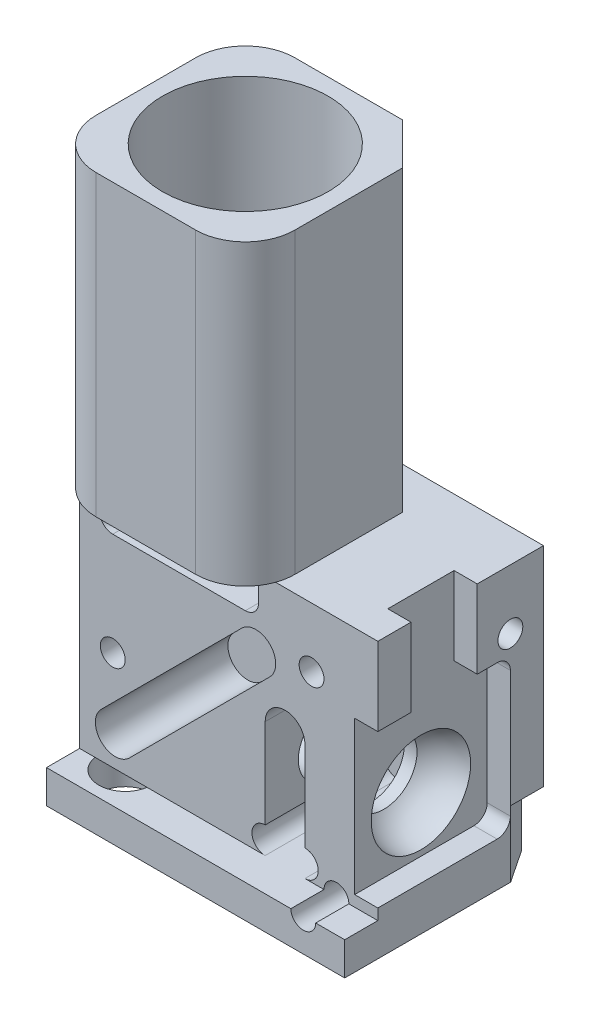
SolidWorks part; units mm, degrees
ref_plane "Front Plane" through (0, 0, 0) normal (0, 0, 1) x (1, 0, 0)
ref_plane "Top Plane" through (0, 0, 0) normal (0, 1, 0) x (1, 0, 0)
ref_plane "Right Plane" through (0, 0, 0) normal (1, 0, 0) x (0, 0, -1)
sketch "Sketch1" plane through (0, 0, 0) normal (0, 1, 0) x (1, 0, 0)
  line L1 (4.5, 3) -> (-4.5, 3)
  line L2 (4.5, 3) -> (4.5, -3)
  line L3 (4.5, -3) -> (-4.5, -3)
  line L4 (-4.5, 3) -> (-4.5, -3)
  line L5 (4.5, 3) -> (-4.5, -3) construction
  line L6 (4.5, -3) -> (-4.5, 3) construction
  point P0 (0, 0)
  dimension "D1" = 6
  dimension "D2" = 9
extrude "Main Body Ext" add sketch "Sketch1" along normal blind 8.3
sketch "Sketch8" plane through (0, 8.3, 0) normal (0, 1, 0) x (1, 0, 0)
  line L0 (0.25, 3) -> (1.5, 1.75)
  line L1 (0.25, 3) -> (-4.5, 3)
  line L2 (1.5, 1.75) -> (1.5, -3)
  line L3 (1.5, -3) -> (-4.5, -3)
  line L4 (-4.5, 3) -> (-4.5, -3)
  line L5 (0.875, 2.375) -> (-4.5, -3) construction
  line L6 (1.5, -3) -> (-4.5, 3) construction
  line L7 (-4.5, 3) -> (-4.5, -3) construction
  line L8 (0, 0) -> (-1.5, 0) construction
  point P0 (-1.5, 0)
  dimension "D1" = 6
  dimension "D2" = 6
  dimension "D3" = 1.25
  dimension "D4" = 3
extrude "Emission Path Ext" add sketch "Sketch8" along normal blind 9
sketch "Sketch3" plane through (0, 0, 0) normal (0, -1, 0) x (1, 0, 0)
  line L0 (-4.5, -3) -> (-4.5, 3) construction
  line L1 (0, 0) -> (-1.5, 0) construction
  circle A0 centre (-1.5, 0) radius 1.25
  dimension "D1" = 3
  dimension "D2" = 2.5
extrude "Emission and Grin Cut" cut sketch "Sketch3" against normal through all
sketch "Sketch4" plane through (4.5, 0, 0) normal (1, 0, 0) x (0, 0, -1)
  line L1 (-3, 0) -> (3, 0) construction
  circle A0 centre (0, 3) radius 1
  dimension "D1" = 2
  dimension "D2" = 3
extrude "Drum Lens Cut" cut sketch "Sketch4" against normal offset from surface (7 mm away) 2 up to face at (-4.5, 8.65, 0)
sketch "Sketch5" plane through (0, 0, 3) normal (0, 0, 1) x (1, 0, 0)
  line L0 (-4.5, 0) -> (4.5, 0) construction
  line L1 (4.5, 8.3) -> (-4.5, 8.3)
  line L2 (4.5, 8.3) -> (4.5, 1)
  line L3 (4.5, 1) -> (-4.5, 1)
  line L4 (-4.5, 8.3) -> (-4.5, 1)
  line L5 (4.5, 8.3) -> (-4.5, 1) construction
  line L6 (4.5, 1) -> (-4.5, 8.3) construction
  line L7 (1.5, 8.3) -> (4.5, 8.3) construction
  line L9 (4.5, 8.3) -> (4.5, 0) construction
  line L10 (-4.5, 17.3) -> (-4.5, 0) construction
  point P0 (0, 4.65)
  dimension "D1" = 1
extrude "FilterSet Cut1" cut sketch "Sketch5" against normal blind 1
sketch "Sketch6" plane through (0, 0, 2) normal (0, 0, 1) x (1, 0, 0)
  line L0 (2.3, 4.5) -> (2.3, 1.8)
  line L1 (1.1, 4.5) -> (2.3, 4.5) construction
  line L2 (2.3, 1) -> (1.1, 1)
  line L3 (-4.5, 1) -> (4.5, 1) construction
  line L4 (-4.5, 8.3) -> (-4.5, 1) construction
  line L5 (-3.9, 7.9) -> (-3.9, 7.5)
  line L6 (1.1, 4.5) -> (1.1, 1.8)
  line L7 (1.5, 8.3) -> (-4.5, 8.3) construction
  line L8 (0.9, 7.9) -> (0.9, 7.5)
  line L9 (-3, 1.5) -> (-3, 1) construction
  line L10 (0.5, 8.3) -> (-3.5, 8.3)
  line L11 (-1.5, 3) -> (-1.5, 1) construction
  line L12 (-1.5, 3) -> (0.4851, 3) construction
  line L13 (0.5, 7.1) -> (-3.5, 7.1)
  line L15 (0.5, 8.3) -> (-3.5, 7.1) construction
  line L16 (0.5, 7.1) -> (-3.5, 8.3) construction
  line L17 (1.1, 1.8) -> (2.3, 1.8) construction
  line L18 (0.3941, 6.5912) -> (-3.8485, 2.3485)
  line L19 (4.5, 1) -> (4.5, 8.3) construction
  line L20 (1.2426, 5.7426) -> (-3, 1.5)
  line L21 (0.3941, 6.5912) -> (-3, 1.5) construction
  line L22 (-3.8485, 2.3485) -> (1.2426, 5.7426) construction
  line L33 (0.5, 8.3) -> (1.102, 8.3) construction
  line L34 (1.102, 8.3) -> (1.102, 7.1) construction
  line L35 (1.102, 7.1) -> (0.5, 7.1) construction
  line L36 (-3.5, 7.1) -> (-4.098, 7.1) construction
  line L37 (-4.098, 7.1) -> (-4.098, 8.3) construction
  line L38 (-4.098, 8.3) -> (-3.5, 8.3) construction
  line L39 (-3.5, 8.3) -> (-2.7284, 6.992) construction
  arc A0 (0.5, 8.3) -> (0.9, 7.9) centre (0.5, 7.9) cw
  arc A1 (1.1, 4.5) -> (2.3, 4.5) centre (1.7, 4.5) cw
  arc A2 (-3.5, 8.3) -> (-3.9, 7.9) centre (-3.5, 7.9) ccw
  arc A3 (0.3941, 6.5912) -> (1.2426, 5.7426) centre (0.8184, 6.1669) cw
  arc A4 (1.1, 1) -> (1.1, 1.8) centre (1.1, 1.4) cw
  arc A5 (-3.8485, 2.3485) -> (-3, 1.5) centre (-3.4243, 1.9243) ccw
  arc A6 (2.3, 1) -> (2.3, 1.8) centre (2.3, 1.4) ccw
  arc A7 (-3.5, 7.1) -> (-3.9, 7.5) centre (-3.5, 7.5) cw
  arc A8 (0.5, 7.1) -> (0.9, 7.5) centre (0.5, 7.5) ccw
  point P5 (-1.5, 7.7)
  point P10 (-1.3029, 4.0456)
  dimension "D10" = 0.5
  dimension "D5" = 2.2
  dimension "D8" = 0.4
  dimension "D11" = 0.4
  dimension "D12" = 0.4
  dimension "D1" = 1.2
  dimension "D2" = 45
  dimension "D3" = 3.5
  dimension "D4" = 1.2
  dimension "D6" = 2
  dimension "D7" = 4
  dimension "D9" = 3
  dimension "D13" = 1.2
  dimension "D14" = 3
  dimension "D15" = 6
extrude "FilterSet Cut2" cut sketch "Sketch6" against normal offset from surface (4 mm away) 1 up to face at (0.4375, 9.2833, -3)
sketch "Sketch10" plane through (0, 17.3, 0) normal (0, 1, 0) x (1, 0, 0)
  line L0 (-1.5, 0) -> (-1.5, -3) construction
  line L1 (-4.5, -3) -> (1.5, -3) construction
  line L3 (-1.5, 0) -> (-4.5, 0) construction
  line L4 (-4.5, 3) -> (-4.5, -3) construction
  circle A0 centre (-1.5, 0) radius 2.5
  dimension "D1" = 5
extrude "Emission Lens Cut" cut sketch "Sketch10" against normal offset from surface (8.5 mm away) 0.5 up to face at (-1.125, 8.3, 1.3125)
sketch "Sketch12" plane through (4.5, 0, 0) normal (1, 0, 0) x (0, 0, -1)
  line L0 (0, 3.635) -> (0, 0) construction
  line L1 (1.6, 5.94) -> (-1.6, 5.94)
  line L2 (1.6, 5.94) -> (1.6, 1.33) construction
  line L3 (-2, 1.33) -> (1.6, 1.33)
  line L4 (-1.6, 5.94) -> (-1.6, 1.33) construction
  line L5 (1.6, 5.94) -> (-1.6, 1.33) construction
  line L6 (1.6, 1.33) -> (-1.6, 5.94) construction
  line L7 (-3, 0) -> (3, 0) construction
  line L9 (-1.6, 5.94) -> (-2, 5.94)
  line L10 (-2, 1) -> (-2, 8.3) construction
  line L11 (-2, 5.94) -> (-2, 1.33)
  line L12 (2, 5.54) -> (2, 1.73)
  arc A1 (1.6, 5.94) -> (2, 5.54) centre (1.6, 5.54) cw
  arc A2 (1.6, 1.33) -> (2, 1.73) centre (1.6, 1.73) ccw
  circle A3 centre (0, 3) radius 1 construction
  point P0 (0, 3.635)
  dimension "D2" = 4.61
  dimension "D3" = 1.67
  dimension "D1" = 3.2
  dimension "D4" = 0.4
sketch "Sketch15" plane through (0, 0, 0) normal (0, -1, 0) x (1, 0, 0)
  line L0 (-3.25, 1.875) -> (-3.25, -1.875) construction
  line L2 (1.5, 0) -> (-1.5, 0) construction
  line L3 (-1.5, 0) -> (-3.25, 0) construction
  circle A0 centre (-3.25, -1.875) radius 0.795
  circle A1 centre (-3.25, 1.875) radius 0.795
  circle A2 centre (1.5, 0) radius 0.795
  dimension "D4" = 1.59
  dimension "D1" = 3.75
  dimension "D2" = 3
  dimension "D3" = 1.75
extrude "Magnets Cut" cut sketch "Sketch15" against normal blind 1
sketch "Sketch18" plane through (0, 0, 2) normal (0, 0, 1) x (1, 0, 0)
  line L0 (-4.5, 8.3) -> (-4.5, 1) construction
  line L1 (4.5, 1) -> (4.5, 8.3) construction
  line L2 (4.5, 8.3) -> (1.5, 8.3) construction
  line L3 (-4.5, 0) -> (4.5, 0) construction
  line L7 (-4.5, 1) -> (-4.0351, 1) construction
  line L9 (-4.5, 1) -> (-4.5, 0) construction
  circle A0 centre (-3.5, 4) radius 0.375
  circle A1 centre (2.5, 6.5) radius 0.375
  circle A2 centre (3.25, 1) radius 0.375
  dimension "D1" = 0.75
  dimension "D2" = 1
  dimension "D3" = 1.8
  dimension "D4" = 2
  dimension "D5" = 3
  dimension "D6" = 1
  dimension "D7" = 7.75
extrude "Screw Holes Cut" cut sketch "Sketch18" against normal blind 3 and the other way through all
fillet "External Fillet 1" radius 1.5 2 edges at (-4.5, 8.65, -3)
sketch "Sketch14" plane through (0, 0, 0) normal (0, -1, 0) x (1, 0, 0)
  line L0 (4.5, -3) -> (4.5, -2.0067)
  line L1 (4.5, 3) -> (4.5, -3) construction
  line L2 (4.5, -2.0067) -> (3.8378, -3)
  line L3 (4.5, -3) -> (-3, -3) construction
  line L4 (3.8378, -3) -> (4.5, -3)
  line L5 (4.5, -3) -> (-4.5, 3) construction
  line L6 (-4.5, -1.5) -> (-4.5, 3) construction
  line L7 (-4.5, 3) -> (4.5, 3) construction
  dimension "D1" = 1.1938
sketch "Sketch28" plane through (0, 7.1, 0) normal (0, 1, 0) x (1, 0, 0)
  circle A0 centre (-1.5, 0) radius 1.5
  dimension "D1" = 3
extrude "Cut-Extrude8" cut sketch "Sketch28" against normal blind 4 and the other way through all
extrude "Cut-Extrude9" cut sketch "Sketch14" against normal blind 2
extrude "Cut-Extrude10" cut sketch "Sketch12" against normal blind 0.7
sketch "Sketch29" plane through (4.5, 0, 0) normal (1, 0, 0) x (0, 0, -1)
  line L0 (3, 8.3) -> (3, 2) construction
  line L1 (-2, 8.3) -> (3, 8.3) construction
  circle A0 centre (2, 6.5) radius 0.375
  dimension "D1" = 0.75
  dimension "D2" = 1
  dimension "D3" = 1.8
extrude "Cut-Extrude11" cut sketch "Sketch29" against normal blind 2.5
sketch "Sketch31" plane through (3.8, 0, 0) normal (1, 0, 0) x (0, 0, -1)
  circle A0 centre (0, 3) radius 1.6
  dimension "D1" = 3.2
sketch "Sketch32" plane through (4.5, 0, 0) normal (1, 0, 0) x (0, 0, -1)
  line L0 (-2, 8.3) -> (3, 8.3) construction
  line L1 (-1, 8.3) -> (1, 8.3)
  line L2 (-1, 8.3) -> (-1, 5.94)
  line L3 (-1, 5.94) -> (1, 5.94)
  line L4 (1, 8.3) -> (1, 5.94)
  line L5 (1.6, 5.94) -> (-2, 5.94) construction
  line L6 (-2, 5.94) -> (-2, 8.3) construction
  line L8 (3, 8.3) -> (3, 2) construction
  dimension "D1" = 1
  dimension "D2" = 2
extrude "Cut-Extrude14" cut sketch "Sketch32" against normal up to surface (0.7 mm away) up to face at (3.8, 3.635, -0.5609)
sketch "Sketch33" plane through (0, 0, 0) normal (0, 0, 1) x (1, 0, 0)
  line L0 (3.8, 3) -> (2.3, 3)
  line L1 (3.8, 1.4) -> (3.8, 4.6) construction
  line L2 (3.8, 3) -> (3.8, 4.5)
  arc A0 (2.3, 3) -> (3.8, 4.5) centre (3.8, 3) cw
  dimension "D2" = 1.5
revolve "Cut-Revolve1" cut sketch "Sketch33" angle 360 about L0
sketch "Sketch36" plane through (0, 17.3, 0) normal (0, 1, 0) x (1, 0, 0)
  line L0 (-4.5, -1.5) -> (-4.5, -3)
  line L1 (-4.5, 1.5) -> (-4.5, -3) construction
  line L2 (-4.5, -3) -> (-3, -3)
  line L3 (-4.5, -3) -> (0, -3) construction
  arc A0 (-4.5, -1.5) -> (-3, -3) centre (-3, -1.5) ccw
  dimension "D1" = 1.5
  dimension "D2" = 1.5
extrude "Cut-Extrude16" cut sketch "Sketch36" against normal up to surface (9 mm away) up to face at (-1.3971, 8.3, 1.2781)
